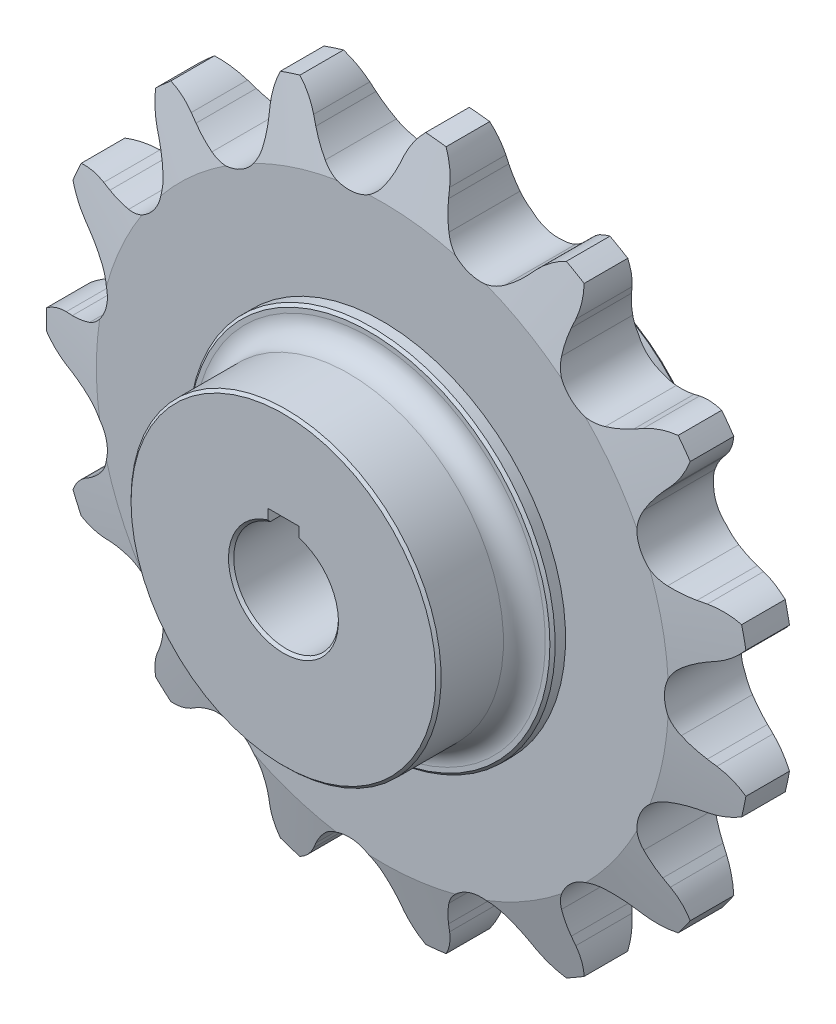
SolidWorks part; units mm, degrees
note: '?' marks a value the reader was unsure of.
ref_plane "Front Plane" through (0, 0, 0) normal (0, 0, 1) x (1, 0, 0)
ref_plane "Top Plane" through (0, 0, 0) normal (0, 1, 0) x (1, 0, 0)
ref_plane "Right Plane" through (0, 0, 0) normal (1, 0, 0) x (0, 0, -1)
ref_axis "Axis1" through (0, 0, 140.661) along (0, 0, -1)?
sketch "SketchRevolveSprocket01" plane through (0, 0, 0) normal (1, 0, 0) x (0, 0, -1)
  line L0 (0, 0) -> (1, 0) construction
  line L1 (-14.6812, 0) -> (-14.6812, 109.3376)
  line L2 (-14.6812, 109.3376) -> (-8.3312, 134.7376)
  line L3 (-8.3312, 134.7376) -> (8.3312, 134.7376)
  line L4 (8.3312, 134.7376) -> (14.6812, 109.3376)
  line L5 (14.6812, 109.3376) -> (14.6812, 0)
  line L6 (14.6812, 0) -> (-14.6812, 0)
  dimension "SprocketSide1" = 14.6812
  dimension "SprocketChamferX" = 6.35
  dimension "SprocketChamferY" = 25.4
  dimension "SprocketOutsideRadius" = 134.7376
  dimension "SprocketTipLength" = 16.6624
  dimension "SprocketSide2" = 14.6812
revolve "ANSI_160__ISO_32A_Chain" add sketch "SketchRevolveSprocket01" angle 360 about L0
sketch "SketchToothSprocket01" plane through (0, 0, 0) normal (0, 0, 1) x (1, 0, 0)
  line L0 (123.8727, 17.3727) -> (120.9653, 16.0737)
  line L1 (120.9653, -16.0737) -> (123.8725, -17.3726)
  arc A0 (132.971, 24.6999) -> (123.8727, 17.3727) centre (113.8497, 39.1308) cw
  arc A1 (120.9653, 16.0737) -> (113.1069, 11.1886) centre (136.5535, -17.7656) ccw
  arc A2 (113.1069, 11.1886) -> (113.1069, -11.1886) centre (122.1673, 0) ccw
  arc A3 (113.1069, -11.1886) -> (120.9653, -16.0737) centre (136.5535, 17.7656) ccw
  arc A4 (123.8725, -17.3726) -> (132.971, -24.6999) centre (113.8497, -39.1308) cw
  arc A5 (132.971, -24.6999) -> (132.971, 24.6999) centre (28.575, 0) ccw
extrude "ToothCutSprocket01" cut sketch "SketchToothSprocket01" against normal blind 14.6812 and the other way blind 14.6812
pattern_circular "Tooth Pattern, 15" count 15 every 24 about axis through (0, 0, 0) along (0, 0, 1) of "ToothCutSprocket01"
sketch "BoreRevolveSketch" plane through (0, 0, 0) normal (1, 0, 0) x (0, 0, -1)
  line L0 (0, 0) -> (1, 0) construction
  line L1 (-14.6812, 0) -> (14.6812, 0)
  line L2 (14.6812, 0) -> (14.6812, 6.35)
  line L3 (14.6812, 6.35) -> (-14.6812, 6.35)
  line L4 (-14.6812, 6.35) -> (-14.6812, 0)
  dimension "BoreSide1" = 14.6812
  dimension "TaperSide1" = 6.35
  dimension "BoreSide2" = 14.6812
  dimension "TaperSide2" = 6.35
revolve "BoreRevolveCut" cut sketch "BoreRevolveSketch" angle 360 about L0
sketch "AuxiliarySketchSprocket01" plane through (0, 0, 0) normal (0, 0, 1) x (1, 0, 0)
  circle A0 centre (0, 0) radius 122.1673 construction
  dimension "PitchDiameter" = 244.3345
sketch "Sketch1" plane through (0, 0, 0) normal (0, 1, 0) x (1, 0, 0)
  line L0 (0, 52.5) -> (0, -52.5) construction
  line L5 (20, -52.5) -> (20, 52.5)
  line L6 (-122.1673, 0) -> (122.1673, 0) construction
  line L8 (0, 0) -> (173.8248, 0) construction
  line L9 (20, 52.5) -> (59.25, 52.5)
  line L10 (59.25, 52.5) -> (59.25, 19.6812)
  line L11 (59.25, 19.6812) -> (70, 19.6812)
  line L12 (70, 19.6812) -> (70, 14.6812)
  line L13 (68.4534, 14.6812) -> (39.6085, 14.6812) construction
  line L14 (97.2127, 14.6812) -> (77.6351, 14.6812) construction
  line L15 (97.2127, 14.6812) -> (77.6351, 14.6812) construction
  line L16 (70, 14.6812) -> (70, -14.6812)
  line L19 (70, -19.6812) -> (70, -14.6812)
  line L20 (59.25, -19.6812) -> (70, -19.6812)
  line L21 (59.25, -52.5) -> (59.25, -19.6812)
  line L22 (20, -52.5) -> (59.25, -52.5)
  point P3 (0, 0)
  point P10 (20, 0)
  point P20 (59.25, 29.5)
  point P23 (66, 19.6812)
  dimension "D9" = 29.3624
  dimension "D1" = 105
  dimension "D2" = 40
  dimension "D3" = 105
  dimension "D4" = 5
  dimension "D5" = 118.5
  dimension "D6" = 23
  dimension "D7" = 132
  dimension "D8" = 140
revolve "Revolve1" add sketch "Sketch1" angle 360 about L0
fillet "Fillet1" radius 8 2 edges at (-59.25, 0, 19.6812) (-59.25, 0, -19.6812)
sketch "Sketch2" plane through (0, 0, -14.6812) normal (0, 0, -1) x (-1, 0, 0)
  line L0 (0, 0) -> (0, 24) construction
  line L1 (6, 19.0788) -> (6, 24)
  line L2 (-6, 19.0788) -> (-6, 24)
  line L3 (6, 0) -> (6, 24) construction
  line L4 (-6, 0) -> (-6, 24) construction
  line L5 (6, 24) -> (-6, 24)
  circle A0 centre (0, 0) radius 20 construction
  circle A1 centre (0, 0) radius 20
  arc A2 (-6, 19.0788) -> (6, 19.0788) centre (0, 0) ccw
  circle M2 centre (0, 0) radius 6.35
  circle M3 centre (0, 0) radius 20
  dimension "D4" = 44
  dimension "D1" = 0
  dimension "D2" = 6
  dimension "D3" = 6
extrude "Cut-Extrude1" cut sketch "Sketch2" against normal through all both and the other way through all contours L1 L5 L2 M3 | M3 M2
chamfer "Chamfer1" distance 1 angle 45 6 edges at (-70, 0, 19.6812) (-59.25, 0, -52.5) (-70, 0, -19.6812) (-59.25, 0, 52.5) (0, -20, 52.5) (0, -20, -52.5)
